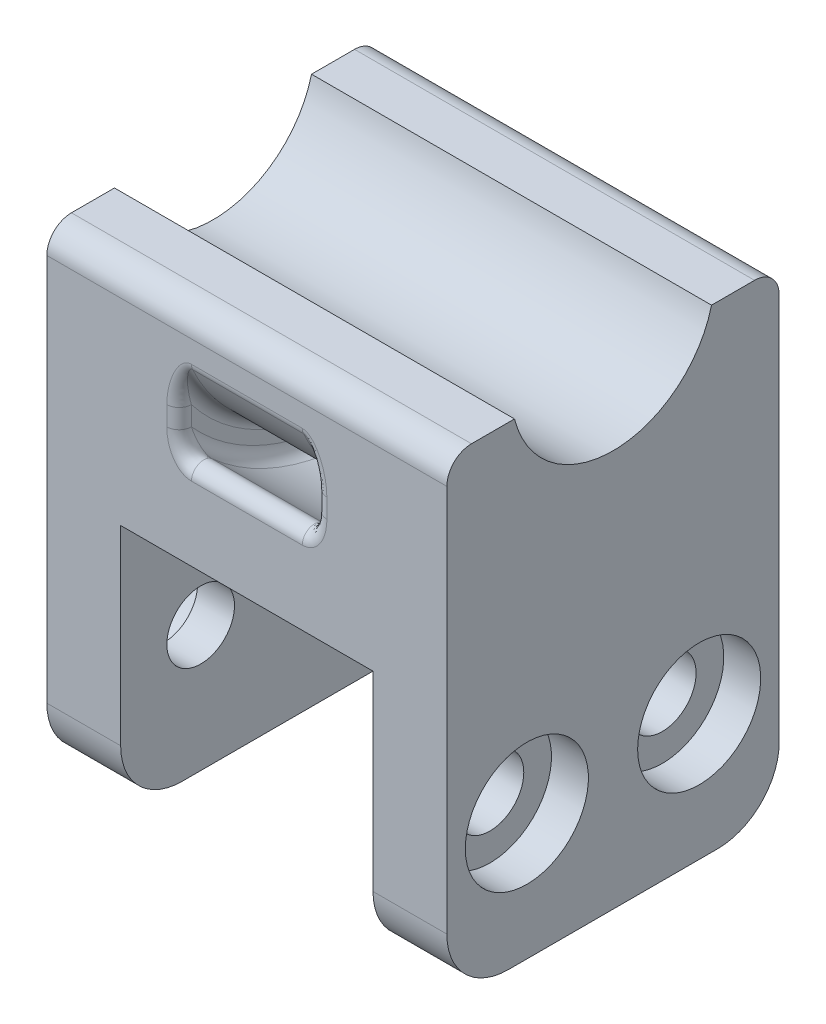
SolidWorks part; units mm, degrees
ref_plane "Спереди" through (0, 0, 0) normal (0, 0, 1) x (1, 0, 0)
ref_plane "Сверху" through (0, 0, 0) normal (0, 1, 0) x (1, 0, 0)
ref_plane "Справа" through (0, 0, 0) normal (1, 0, 0) x (0, 0, -1)
sketch "Эскиз1" plane through (0, 0, 0) normal (0, 1, 0) x (1, 0, 0)
  line L1 (-10.25, 13.5) -> (10.25, 13.5)
  line L2 (-10.25, 13.5) -> (-10.25, -13.5)
  line L3 (-10.25, -13.5) -> (10.25, -13.5)
  line L4 (10.25, 13.5) -> (10.25, -13.5)
  line L5 (-10.25, 13.5) -> (10.25, -13.5) construction
  line L6 (-10.25, -13.5) -> (10.25, 13.5) construction
  point P0 (0, 0)
  dimension "D1" = 27
  dimension "D2" = 20.5
extrude "Бобышка-Вытянуть1" add sketch "Эскиз1" along normal blind 18
sketch "Эскиз2" plane through (-10.25, 0, 0) normal (-1, 0, 0) x (0, 0, 1)
  line L0 (-13.5, 18) -> (13.5, 18) construction
  circle A0 centre (0, 20) radius 8.25
  dimension "D1" = 16.5
  dimension "D2" = 2
extrude "Вырез-Вытянуть1" cut sketch "Эскиз2" against normal through all
sketch "Эскиз3" plane through (0, 0, 0) normal (1, 0, 0) x (0, 0, -1)
  line L0 (-13.5, 18) -> (-13.5, 14) construction
  line L1 (-13.5, 18) -> (-13.5, 0) construction
  circle A0 centre (0, 20) radius 14.7733
  circle A1 centre (0, 20) radius 17.7733
  arc A2 (-8.0039, 18) -> (8.0039, 18) centre (0, 20) ccw construction
  dimension "D1" = 4
  dimension "D2" = 3
extrude "Вырез-Вытянуть2" cut sketch "Эскиз3" against normal mid plane 11
fillet "Скругление1" radius 1 12 edges at (0, 8.4397, -13.5) (5.5, 2.2267, 0) (0, 8.4397, 13.5) (-5.5, 2.2267, 0) (-5.5, 5.2267, 0) (0, 14, 13.5) (5.5, 5.2267, 0) (0, 14, -13.5) (-5.5, 11.2199, 13.5) (-5.5, 11.2199, -13.5) (5.5, 11.2199, 13.5) (5.5, 11.2199, -13.5)
sketch "Эскиз4" plane through (-10.25, 0, 0) normal (-1, 0, 0) x (0, 0, 1)
  line L1 (13.5, -20.5) -> (-13.5, -20.5)
  line L2 (13.5, -20.5) -> (13.5, 0)
  line L3 (13.5, 0) -> (-13.5, 0)
  line L4 (-13.5, -20.5) -> (-13.5, 0)
  line L5 (13.5, -20.5) -> (-13.5, 0) construction
  line L6 (13.5, 0) -> (-13.5, -20.5) construction
  line L11 (-13.5, -10.25) -> (13.5, -10.25) construction
  line L12 (0, 0) -> (0, -20.5) construction
  line L16 (13.5, 18) -> (8.0039, 18)
  line L17 (-8.0039, 18) -> (-13.5, 18)
  line L18 (-13.5, 18) -> (-13.5, 0)
  line L19 (-13.5, 0) -> (13.5, 0)
  line L20 (13.5, 0) -> (13.5, 18)
  line L21 (13.5, 18) -> (8.0039, 18)
  line L22 (-8.0039, 18) -> (-13.5, 18)
  line L23 (-13.5, 18) -> (-13.5, 0)
  line L24 (-13.5, 0) -> (13.5, 0)
  line L25 (13.5, 0) -> (13.5, 18)
  circle A1 centre (-7, -10.25) radius 2.75
  arc A2 (-8.0039, 18) -> (8.0039, 18) centre (0, 20) ccw
  arc A3 (-8.0039, 18) -> (8.0039, 18) centre (0, 20) ccw
  circle A4 centre (7, -10.25) radius 2.75
  point P0 (0, -10.25)
  line M13 (13.5, 18) -> (8.0039, 18)
  arc M14 (8.0039, 18) -> (-8.0039, 18) centre (0, 20) cw
  line M15 (-8.0039, 18) -> (-13.5, 18)
  line M16 (-13.5, 18) -> (-13.5, 0)
  line M17 (-13.5, 0) -> (13.5, 0)
  line M18 (13.5, 0) -> (13.5, 18)
  dimension "D4" = 5.5
  dimension "D1" = 20.5
  dimension "D3" = 14
extrude "Бобышка-Вытянуть2" add sketch "Эскиз4" along normal blind 6 contours M18 M13 M14 M15 M16 M17 | L4 L1 L2 A4 A1 M17 region at (-10.25, -10.25, 0) region at (-10.25, 7.8469, 0)
sketch "Эскиз5" plane through (-16.25, 0, 0) normal (-1, 0, 0) x (0, 0, 1)
  circle A0 centre (-7, -10.25) radius 5
  circle A1 centre (7, -10.25) radius 5
  dimension "D1" = 10
  dimension "D2" = 10
extrude "Вырез-Вытянуть3" cut sketch "Эскиз5" against normal blind 3
fillet "Скругление2" radius 5 2 edges at (-13.25, -20.5, 13.5) (-13.25, -20.5, -13.5)
mirror "Зеркальное отражение1" about plane through (0, 0, 0) normal (1, 0, 0) of "Бобышка-Вытянуть2", "Вырез-Вытянуть3", "Скругление2"
fillet "Скругление3" radius 2 2 edges at (0, 18, 13.5) (0, 18, -13.5)
equation "\"print_offset\"= 0.5"
equation "\"screw_m5_d\"= 5"
equation "\"screw_m5_hh_d\"= 9.5"
equation "\"nut_m5_d\"= 7.9"
equation "\"nut_m5_h\"= 3.9"
equation "\"tube_d\"= 16"
equation "\"tube_tape_d\"= 3"
equation "\"tube_tape_h\"= 11"
equation "\"D1@Эскиз2\"=\"tube_d\"+\"print_offset\""
equation "\"D2@Эскиз3\"=\"tube_tape_d\""
equation "\"D1@Вырез-Вытянуть2\"=\"tube_tape_h\""
equation "\"D1@Эскиз4\"=\"print_offset\"+20"
equation "\"D3@Эскиз4\"=14"
equation "\"D4@Эскиз4\"=\"screw_m5_d\"+\"print_offset\""
equation "\"D1@Эскиз5\"=\"screw_m5_hh_d\"+\"print_offset\""
equation "\"D2@Эскиз5\"=\"D1@Эскиз5\""
equation "\"D2@Эскиз1\"=\"print_offset\"+20"
